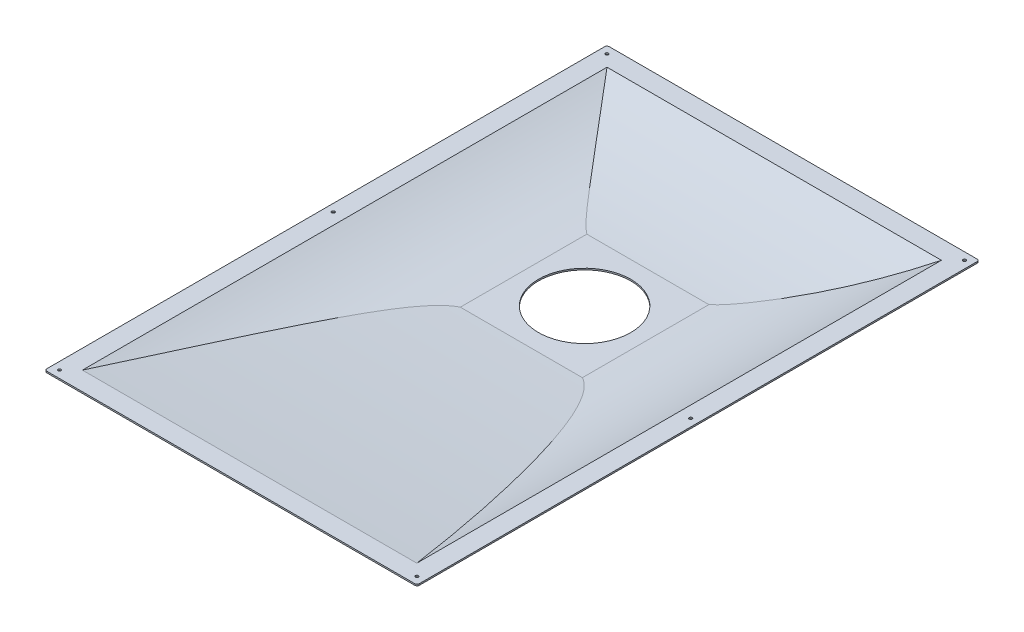
SolidWorks part; units mm, degrees
ref_plane "Ön Düzlem" through (0, 0, 0) normal (0, 0, 1) x (1, 0, 0)
ref_plane "Üst Düzlem" through (0, 0, 0) normal (0, 1, 0) x (1, 0, 0)
ref_plane "Sağ Düzlem" through (0, 0, 0) normal (1, 0, 0) x (0, 0, -1)
sketch "Sketch1" plane through (0, 0, 0) normal (0, 1, 0) x (1, 0, 0)
  line L1 (-250, -375) -> (0, -375)
  line L2 (-250, -375) -> (-250, 380)
  line L3 (-250, 380) -> (0, 380)
  line L4 (0, -375) -> (0, 380)
  line L5 (-250, -375) -> (0, 380) construction
  line L6 (-250, 380) -> (0, -375) construction
  point P0 (0, 0)
  dimension "D1" = 250
  dimension "D2" = 755
  dimension "D3" = 250
extrude "Boss-Extrude1" add sketch "Sketch1" along normal blind 40
sketch "Sketch2" plane through (0, 0, 0) normal (0, -1, 0) x (1, 0, 0)
  circle A0 centre (0, -100) radius 62
  dimension "D1" = 100
ref_plane "Plane1" through (0, 0, -100) normal (0, 0, 1) x (1, 0, 0)
sketch "Sketch6" plane through (0, 0, -100) normal (0, 0, 1) x (1, 0, 0)
  line L0 (-62, 0) -> (62, 0) construction
  line L1 (-250, 0) -> (0, 0) construction
  line L2 (-250, 40) -> (0, 40) construction
  line L3 (-225, 38) -> (-250, 38)
  line L4 (-250, 40) -> (-250, 0) construction
  line L5 (-250, 38) -> (-250, 40)
  line L6 (-82, 0) -> (0, 0)
  line L7 (0, 0) -> (0, -20.1592)
  line L8 (0, -20.1592) -> (-273.2342, -20.1592)
  line L9 (-273.2342, -20.1592) -> (-273.2342, 40)
  line L10 (-273.2342, 40) -> (-250, 40)
  arc A0 (-225, 38) -> (-82, 0) centre (-69.3823, 335.548) ccw
  dimension "D1" = 2
  dimension "D2" = 25
extrude "Cut-Extrude1" cut sketch "Sketch6" against normal through all both and the other way through all contours L9 L10 L5 L3 A0 L6 L7 L8
mirror "Mirror2" about plane through (0, 0, 0) normal (1, 0, 0) of "Cut-Extrude1", "Boss-Extrude1"
sketch "Sketch9" plane through (0, 0, 0) normal (1, 0, 0) x (0, 0, -1)
  line L0 (185, 0) -> (15, 0)
  line L1 (38, 0) -> (162, 0) construction
  line L2 (380, 38) -> (-375, 38) construction
  line L3 (355, 38) -> (394.867, 38)
  line L4 (394.867, 38) -> (394.867, -19.964)
  line L5 (394.867, -19.964) -> (-417.3641, -19.964)
  line L6 (-417.3641, -19.964) -> (-417.3641, 38)
  line L7 (380, 38) -> (-375, 38) construction
  line L8 (-350, 38) -> (-417.3641, 38)
  line L11 (380, 0) -> (-375, 0) construction
  line L12 (100, 22) -> (100, -22) construction
  arc A0 (185, 0) -> (355, 38) centre (158.4306, 518.1264) ccw
  arc A1 (15, 0) -> (-350, 38) centre (392.4007, 5396.9938) cw
  point P15 (100, 0)
  dimension "D1" = 25
  dimension "D2" = 25
extrude "Cut-Extrude2" cut sketch "Sketch9" against normal through all both and the other way through all
shell "Shell1" thickness 2 removed face at (0, 40, -2.5)
extrude "Cut-Extrude6" cut sketch "Sketch2" against normal up to next
sketch "Sketch10" plane through (0, 40, 0) normal (0, 1, 0) x (1, 0, 0)
  line L0 (-224.5078, 2.372) -> (-250, 2.5) construction
  line L1 (-224.5078, 354.606) -> (-224.5078, -349.8621) construction
  line L2 (-250, 380) -> (-250, -375) construction
  line L3 (-250, -375) -> (-224.5078, -349.8621) construction
  line L4 (0, 380) -> (0, -375) construction
  line L5 (250, 380) -> (-250, 380) construction
  line L8 (-250, -375) -> (250, -375) construction
  line L9 (-224.5078, 354.606) -> (-250, 380) construction
  circle A0 centre (-240, 2.4498) radius 2
  circle A1 centre (-240, -365.139) radius 2
  circle A2 centre (240, 370.0385) radius 2
  circle A3 centre (240, 2.4498) radius 2
  circle A4 centre (240, -365.139) radius 2
  circle A5 centre (-240, 370.0385) radius 2
  dimension "D1" = 10
  dimension "D2" = 10
  dimension "D6" = 10
extrude "Cut-Extrude7" cut sketch "Sketch10" against normal up to next
fillet "Fillet1" radius 3 4 edges at (-250, 39, 375) (250, 39, 375) (250, 39, -380) (-250, 39, -380)
